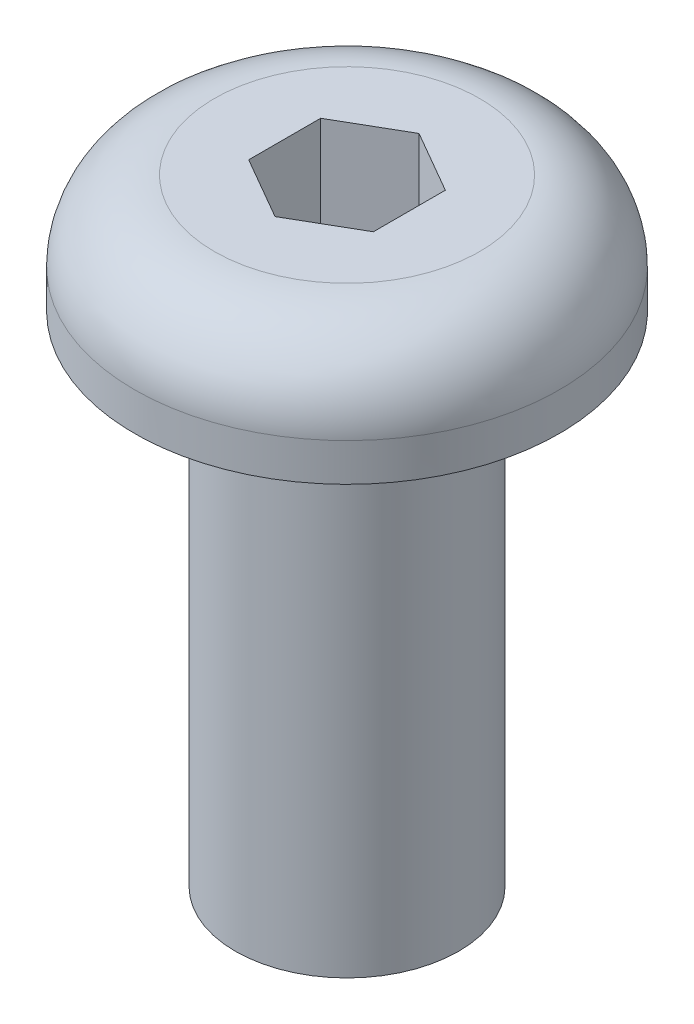
SolidWorks part; units mm, degrees
ref_plane "Front Plane" through (0, 0, 0) normal (0, 0, 1) x (1, 0, 0)
ref_plane "Top Plane" through (0, 0, 0) normal (0, 1, 0) x (1, 0, 0)
ref_plane "Right Plane" through (0, 0, 0) normal (1, 0, 0) x (0, 0, -1)
sketch "Sketch1" plane through (0, 0, 0) normal (0, 1, 0) x (1, 0, 0)
  circle A0 centre (0, 0) radius 1.4224
  dimension "D1" = 2.8448
extrude "Boss-Extrude1" add sketch "Sketch1" along normal blind 6.35
sketch "Sketch2" plane through (0, 6.35, 0) normal (0, 1, 0) x (1, 0, 0)
  circle A0 centre (0, 0) radius 2.7051
  dimension "D1" = 5.4102
extrude "Boss-Extrude2" add sketch "Sketch2" along normal blind 1.4986
fillet "Fillet1" radius 1.016 1 edges at (0, 7.8486, 2.7051)
sketch "Sketch3" plane through (0, 7.8486, 0) normal (0, 1, 0) x (1, 0, 0)
  line L1 (0, 0.9165) -> (-0.7937, 0.4583)
  line L2 (-0.7937, 0.4583) -> (-0.7937, -0.4583)
  line L3 (-0.7937, -0.4583) -> (0, -0.9165)
  line L4 (0, -0.9165) -> (0.7938, -0.4583)
  line L5 (0.7938, -0.4583) -> (0.7938, 0.4583)
  line L6 (0.7938, 0.4583) -> (0, 0.9165)
  circle A0 centre (0, 0) radius 0.7937 construction
  dimension "D1" = 1.5875
extrude "Cut-Extrude1" cut sketch "Sketch3" against normal blind 2.3813
